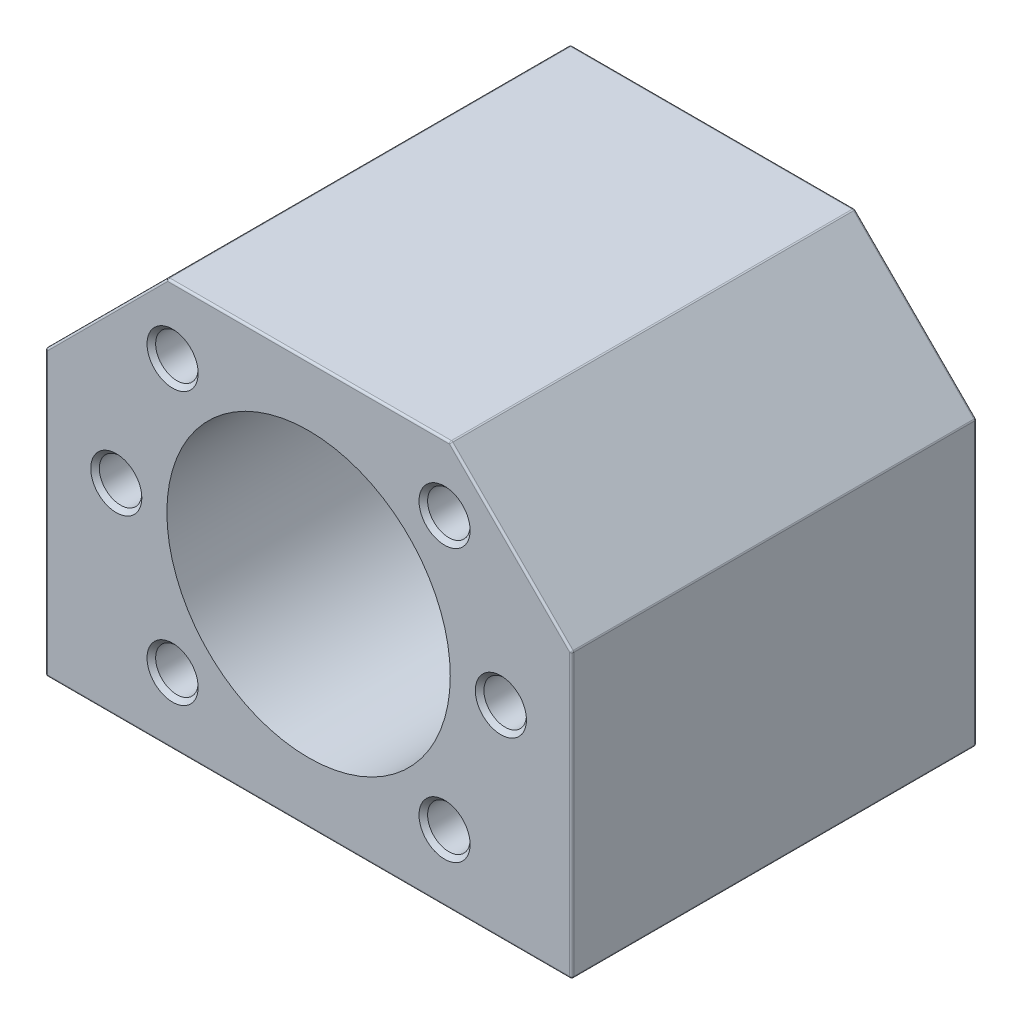
SolidWorks part; units mm, degrees
ref_plane "Plan de face" through (0, 0, 0) normal (0, 0, 1) x (1, 0, 0)
ref_plane "Plan de dessus" through (0, 0, 0) normal (0, 1, 0) x (1, 0, 0)
ref_plane "Plan de droite" through (0, 0, 0) normal (1, 0, 0) x (0, 0, -1)
sketch "Esquisse1" plane through (0, 0, 0) normal (0, 0, 1) x (1, 0, 0)
  line L1 (0, 0) -> (52, 0)
  line L2 (0, 0) -> (0, 40)
  line L3 (0, 40) -> (52, 40)
  line L4 (52, 0) -> (52, 40)
  circle A0 centre (26, 20) radius 14
  point P7 (26, 0)
  point P9 (0, 20)
  dimension "D1" = 52
  dimension "D3" = 28
  dimension "D2" = 40
extrude "Boss.-Extru.1" add sketch "Esquisse1" along normal blind 40
chamfer "Chanfrein1" distance 12 angle 45 2 edges at (0, 40, 20) (52, 40, 20)
fillet "Congé1" radius 0.2 19 edges at (52, 14, 0) (46, 34, 0) (26, 40, 0) (6, 34, 0) (0, 14, 0) (52, 28, 20) (40, 40, 20) (12, 40, 20) (0, 28, 20) (6, 34, 40) (26, 40, 40) (46, 34, 40) (52, 14, 40) (52, 0, 20) (26, 0, 0) (0, 14, 40) (0, 0, 20) (26, 0, 40) (40, 20, 0)
sketch "Эскиз1" plane through (0, 0, 0) normal (0, -1, 0) x (1, 0, 0)
  line L0 (0.2, 40) -> (51.8, 40) construction
  line L1 (6, 32) -> (46, 32) construction
  line L2 (6, 32) -> (6, 8) construction
  line L3 (6, 8) -> (46, 8) construction
  line L4 (46, 32) -> (46, 8) construction
  line L5 (51.8, 0) -> (0.2, 0) construction
  line L6 (26, 40) -> (26, 0) construction
  point P10 (26, 32)
  dimension "D1" = 24
  dimension "D2" = 40
  dimension "D3" = 8
hole_wizard "Отверстие обработанное метчиком M5x0.81" positions "Эскиз2" profile "Эскиз3" tap size "M5x0.8" standard "Ansi Metric"
sketch "Эскиз2" plane through (0, 0, 0) normal (0, -1, 0) x (-1, 0, 0)
  point P0 (-6, -32)
  point P3 (-46, -32)
  point P6 (-46, -8)
  point P9 (-6, -8)
sketch "Эскиз3" plane through (6, 0, 32) normal (1, 0, 0) x (0, 0, -1)
  line L0 (0, 0) -> (0, 15.2618)
  line L1 (0, 15.2618) -> (2.1, 14)
  line L2 (2.1, 14) -> (2.1, 0.425)
  line L3 (2.1, 0.425) -> (2.525, 0)
  line L5 (2.525, 0) -> (0, 0)
  line L6 (-2.1, 0.425) -> (-2.525, 0) construction
  line L10 (0, 15.2618) -> (-2.1, 14) construction
  line L11 (0, -6.35) -> (0, 107.95) construction
  dimension "Диаметр сверла" = 4.2
  dimension "Глубина сверла" = 14
  dimension "Диаметр передней зенковки" = 5.05
  dimension "Угол передней зенковки" = 90
  dimension "Угол заточки сверла" = 118
cosmetic thread "Отверстие резьбы1" parameters "D1"=10, "D2"=5
cosmetic thread "Отверстие резьбы2" parameters "D1"=10, "D2"=5
cosmetic thread "Отверстие резьбы3" parameters "D1"=10, "D2"=5
cosmetic thread "Отверстие резьбы4" parameters "D1"=10, "D2"=5
sketch "Эскиз4" plane through (0, 0, 40) normal (0, 0, 1) x (1, 0, 0)
  line L0 (6, 0) -> (46, 0) construction
  line L1 (26, 40) -> (26, 0) construction
  line L2 (12.0828, 40) -> (39.9172, 40) construction
  circle A0 centre (26, 20) radius 19 construction
  point P4 (7, 20)
  point P5 (45, 20)
  dimension "D1" = 38
  dimension "D2" = 20
hole_wizard "Отверстие обработанное метчиком M5x0.82" positions "Эскиз5" profile "Эскиз6" tap size "M5x0.8" standard "Ansi Metric"
sketch "Эскиз5" plane through (0, 0, 40) normal (0, 0, 1) x (1, 0, 0)
  point P0 (7, 20)
  point P3 (45, 20)
sketch "Эскиз6" plane through (7, 20, 40) normal (1, 0, 0) x (0, -1, 0)
  line L0 (0, 0) -> (0, 15.2618)
  line L1 (0, 15.2618) -> (2.1, 14)
  line L2 (2.1, 14) -> (2.1, 0.425)
  line L3 (2.1, 0.425) -> (2.525, 0)
  line L5 (2.525, 0) -> (0, 0)
  line L6 (-2.1, 0.425) -> (-2.525, 0) construction
  line L10 (0, 15.2618) -> (-2.1, 14) construction
  line L11 (0, -6.35) -> (0, 107.95) construction
  dimension "Диаметр сверла" = 4.2
  dimension "Глубина сверла" = 14
  dimension "Диаметр передней зенковки" = 5.05
  dimension "Угол передней зенковки" = 90
  dimension "Угол заточки сверла" = 118
cosmetic thread "Отверстие резьбы5" parameters "D1"=10, "D2"=5
cosmetic thread "Отверстие резьбы6" parameters "D1"=10, "D2"=5
ref_axis "Ось1" through (26, 20, 40) along (0, 0, 1)
pattern_circular "Круговой массив1" count 2 every 45 about axis through (26, 20, 40) along (0, 0, 1) of "Отверстие обработанное метчиком M5x0.82"
pattern_circular "Круговой массив2" count 2 every 315 about axis through (26, 20, 40) along (0, 0, 1) of "Отверстие обработанное метчиком M5x0.82"
ref_plane "Плоскость1" through (26, 0, 0) normal (-1, 0, 0) x (0, 0, -1)
